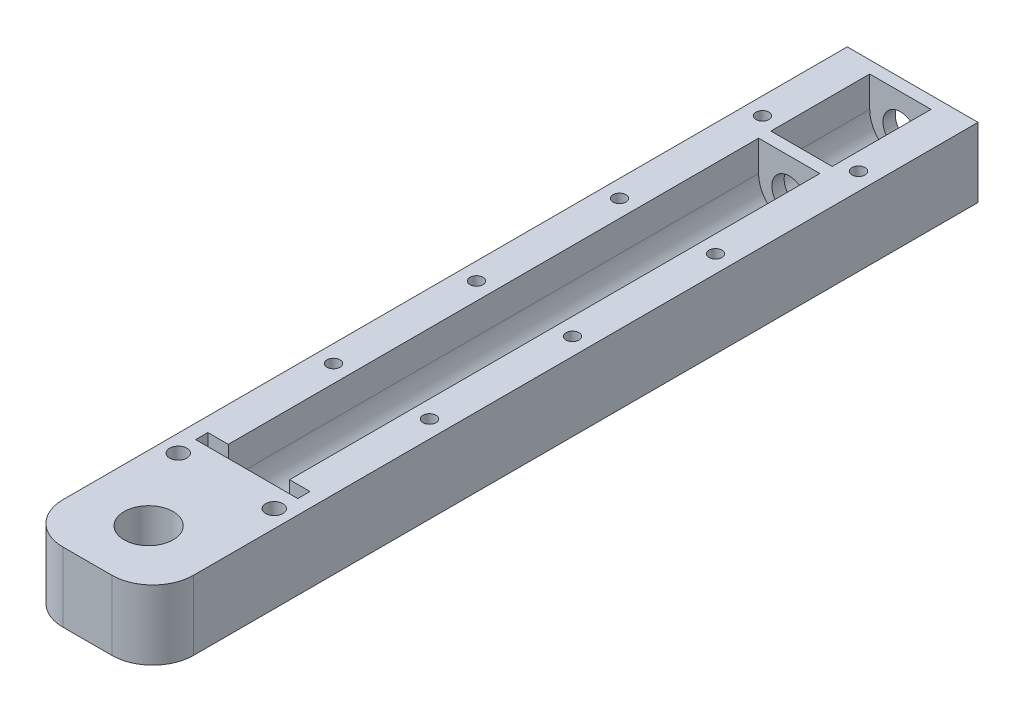
SolidWorks part; units mm, degrees
ref_plane "Front Plane" through (0, 0, 0) normal (0, 0, 1) x (1, 0, 0)
ref_plane "Top Plane" through (0, 0, 0) normal (0, 1, 0) x (1, 0, 0)
ref_plane "Right Plane" through (0, 0, 0) normal (1, 0, 0) x (0, 0, -1)
sketch "Sketch1" plane through (0, 0, 0) normal (0, 0, 1) x (1, 0, 0)
  line L1 (-16, 8.5) -> (16, 8.5)
  line L2 (-16, 8.5) -> (-16, -8.5)
  line L3 (-16, -8.5) -> (16, -8.5)
  line L4 (16, 8.5) -> (16, -8.5)
  line L5 (-16, 8.5) -> (16, -8.5) construction
  line L6 (-16, -8.5) -> (16, 8.5) construction
  circle A0 centre (0, 0) radius 4.25
  point P0 (0, 0)
  dimension "D3" = 8.5
  dimension "D1" = 17
  dimension "D2" = 32
extrude "Boss-Extrude1" add sketch "Sketch1" along normal blind 3
sketch "Sketch2" plane through (0, 0, 3) normal (0, 0, 1) x (1, 0, 0)
  line L0 (-7.5, 1) -> (-7.5, 8.5)
  line L1 (16, -8.5) -> (-16, -8.5)
  line L2 (16, -8.5) -> (16, 8.5)
  line L3 (16, 8.5) -> (7.5, 8.5)
  line L4 (-16, -8.5) -> (-16, 8.5)
  line L5 (16, -8.5) -> (-16, 8.5) construction
  line L6 (16, 8.5) -> (-16, -8.5) construction
  line L7 (7.5, 1) -> (7.5, 8.5)
  line L8 (-16, 8.5) -> (-7.5, 8.5)
  arc A0 (-7.5, 1) -> (7.5, 1) centre (0, 1) ccw
  point P0 (0, 0)
  point P9 (0, -6.5)
  dimension "D1" = 15
  dimension "D2" = 2
extrude "Boss-Extrude2" add sketch "Sketch2" along normal blind 24.2
sketch "Sketch3" plane through (0, 0, 27.2) normal (0, 0, 1) x (1, 0, 0)
  line L1 (-16, -8.5) -> (16, -8.5)
  line L2 (-16, -8.5) -> (-16, 8.5)
  line L3 (-16, 8.5) -> (16, 8.5)
  line L4 (16, -8.5) -> (16, 8.5)
  line L5 (-16, -8.5) -> (16, 8.5) construction
  line L6 (-16, 8.5) -> (16, -8.5) construction
  circle A0 centre (0, 0) radius 4.25
extrude "Boss-Extrude3" add sketch "Sketch3" along normal blind 3
sketch "Sketch4" plane through (0, 0, 30.2) normal (0, 0, 1) x (1, 0, 0)
  line L1 (16, -8.5) -> (-16, -8.5)
  line L2 (16, -8.5) -> (16, 8.5)
  line L3 (16, 8.5) -> (7.5, 8.5)
  line L4 (-16, -8.5) -> (-16, 8.5)
  line L5 (16, -8.5) -> (-16, 8.5) construction
  line L6 (16, 8.5) -> (-16, -8.5) construction
  line L7 (-7.5, 1) -> (-7.5, 8.5)
  line L8 (7.5, 1) -> (7.5, 8.5)
  line L9 (-7.5, 8.5) -> (-16, 8.5)
  arc A0 (-7.5, 1) -> (7.5, 1) centre (0, 1) ccw
  point P0 (0, 0)
  point P8 (0, -6.5)
  point P13 (0, 8.5)
  dimension "D1" = 15
  dimension "D2" = 2
extrude "Boss-Extrude4" add sketch "Sketch4" along normal blind 129.8
sketch "Sketch5" plane through (0, 0, 160) normal (0, 0, 1) x (1, 0, 0)
  line L1 (16, -8.5) -> (-16, -8.5)
  line L2 (16, -8.5) -> (16, 8.5)
  line L3 (16, 8.5) -> (-16, 8.5)
  line L4 (-16, -8.5) -> (-16, 8.5)
  line L5 (16, -8.5) -> (-16, 8.5) construction
  line L6 (16, 8.5) -> (-16, -8.5) construction
  point P0 (0, 0)
extrude "Boss-Extrude5" add sketch "Sketch5" along normal blind 18
sketch "Sketch6" plane through (0, 8.5, 0) normal (0, 1, 0) x (1, 0, 0)
  line L0 (7.5, -160) -> (-7.5, -160) construction
  line L1 (-12.5, -160) -> (12.5, -160)
  line L2 (-12.5, -160) -> (-12.5, -163)
  line L3 (-12.5, -163) -> (12.5, -163)
  line L4 (12.5, -160) -> (12.5, -163)
  line L6 (7.5, -160) -> (-7.5, -160) construction
  point P6 (0, -160)
  point P10 (0, -160)
  dimension "D1" = 3
  dimension "D2" = 25
extrude "Cut-Extrude1" cut sketch "Sketch6" against normal blind 15
sketch "Sketch7" plane through (0, 8.5, 0) normal (0, 1, 0) x (1, 0, 0)
  line L1 (-16, -178) -> (16, -178)
  line L2 (-16, -178) -> (-16, -192)
  line L3 (-6, -202) -> (6, -202)
  line L4 (16, -178) -> (16, -192)
  arc A0 (16, -192) -> (6, -202) centre (6, -192) cw
  arc A1 (-16, -192) -> (-6, -202) centre (-6, -192) ccw
  point P6 (16, -178)
  dimension "D1" = 10
  dimension "D2" = 24
extrude "Boss-Extrude6" add sketch "Sketch7" against normal up to vertex (17 mm away) up to point (-16, -8.5, 178)
sketch "Sketch8" plane through (0, 8.5, 0) normal (0, 1, 0) x (1, 0, 0)
  line L0 (0, -202) -> (0, -187) construction
  line L1 (-6, -202) -> (6, -202) construction
  circle A0 centre (0, -187) radius 6
  dimension "D1" = 12
  dimension "D2" = 15
extrude "Cut-Extrude2" cut sketch "Sketch8" against normal blind 46
sketch "Sketch9" plane through (0, 8.5, 0) normal (0, 1, 0) x (1, 0, 0)
  line L0 (0, -202) -> (0, -30.2) construction
  line L1 (-7.5, -30.2) -> (7.5, -30.2) construction
  line L2 (11.75, -130) -> (11.75, -95) construction
  line L3 (-12.5, -163) -> (12.5, -163) construction
  line L4 (7.5, -160) -> (16, -160)
  line L5 (11.75, -160) -> (11.75, -130) construction
  line L6 (-16, 0) -> (-16, -192)
  line L7 (-6, -202) -> (6, -202)
  line L8 (16, -192) -> (16, 0)
  line L9 (16, 0) -> (-16, 0)
  line L10 (-16, 0) -> (-16, -192)
  line L11 (-6, -202) -> (6, -202)
  line L12 (16, -192) -> (16, 0)
  line L13 (16, 0) -> (-16, 0)
  circle A0 centre (11.75, -130) radius 1.5875
  circle A1 centre (-11.75, -130) radius 1.5875
  arc A2 (-16, -192) -> (-6, -202) centre (-6, -192) ccw
  arc A3 (6, -202) -> (16, -192) centre (6, -192) ccw
  arc A4 (-16, -192) -> (-6, -202) centre (-6, -192) ccw
  arc A5 (6, -202) -> (16, -192) centre (6, -192) ccw
  circle A6 centre (11.75, -95) radius 1.5875
  circle A7 centre (-11.75, -95) radius 1.5875
  circle A8 centre (11.75, -60) radius 1.5875
  circle A9 centre (11.75, -25) radius 1.5875
  circle A14 centre (-11.75, -25) radius 1.5875
  circle A15 centre (-11.75, -60) radius 1.5875
  circle A16 centre (11.75, 10) radius 1.5875 [skipped]
  circle A17 centre (11.75, 45) radius 1.5875 [skipped]
  circle A18 centre (11.75, -168) radius 2.1143
  circle A19 centre (-11.75, -168) radius 2.1143
  circle A20 centre (0, -187) radius 6 construction
  circle A21 centre (0, -187) radius 6
  point P35 (0, -181)
  dimension "D3" = 3.175
  dimension "D5" = 3.175
  dimension "D7" = 35
  dimension "D8" = 4.2287
  dimension "D9" = 38
  dimension "D1" = 0
  dimension "D2" = 30
  dimension "D4" = 35
  dimension "D10" = 25
  dimension "D11" = 18
  dimension "D6" = 5
extrude "Cut-Extrude3" cut sketch "Sketch9" against normal blind 46 contours A0 | A6 | A1 | A7 | A15 | A8 | A9 | A14 | A18 | A19 region at (11.75, 8.5, 130) region at (-11.75, 8.5, 130) region at (11.75, 8.5, 95) region at (-11.75, 8.5, 95) region at (11.75, 8.5, 60) region at (11.75, 8.5, 25) region at (-11.75, 8.5, 25) region at (-11.75, 8.5, 60) region at (11.75, 8.5, 168)
sketch "Sketch10" plane through (0, -8.5, 0) normal (0, -1, 0) x (1, 0, 0)
  line L0 (-15.214, 25) -> (-13.482, 22)
  line L1 (-13.482, 28) -> (-10.018, 28)
  line L3 (-13.482, 22) -> (-10.018, 22)
  line L5 (-13.482, 22) -> (-10.018, 28) construction
  line L6 (-13.482, 28) -> (-10.018, 22) construction
  line L7 (-8.286, 25) -> (-10.018, 22)
  line L8 (-15.214, 25) -> (-13.482, 28)
  line L9 (-8.286, 25) -> (-10.018, 28)
  line L10 (0, 0) -> (0, 202) construction
  line L11 (-16, 0) -> (16, 0) construction
  line L12 (-6, 202) -> (6, 202) construction
  line L13 (13.482, 28) -> (10.018, 28)
  line L14 (8.286, 25) -> (10.018, 28)
  line L15 (8.286, 25) -> (10.018, 22)
  line L16 (13.482, 22) -> (10.018, 22)
  line L17 (15.214, 25) -> (13.482, 22)
  line L18 (15.214, 25) -> (13.482, 28)
  line L61 (13.482, 171.2837) -> (10.018, 171.2837)
  line L62 (8.286, 168.2837) -> (10.018, 171.2837)
  line L63 (8.286, 168.2837) -> (10.018, 165.2837)
  line L64 (13.482, 165.2837) -> (10.018, 165.2837)
  line L65 (15.214, 168.2837) -> (13.482, 165.2837)
  line L66 (15.214, 168.2837) -> (13.482, 171.2837)
  line L70 (-11.75, 95) -> (-11.75, 135.0869) construction
  line L71 (-10.0179, 57) -> (-8.2859, 60)
  line L81 (-8.2859, 60) -> (-10.0179, 63)
  line L82 (-10.0179, 63) -> (-13.4821, 63)
  line L83 (-13.4821, 63) -> (-15.2141, 60)
  line L84 (-15.2141, 60) -> (-13.4821, 57)
  line L85 (-13.4821, 57) -> (-10.0179, 57)
  line L86 (13.4821, 57) -> (15.2141, 60)
  line L87 (15.2141, 60) -> (13.4821, 63)
  line L88 (13.482, 135.4628) -> (10.018, 135.4628) [skipped]
  line L89 (8.286, 132.4628) -> (10.018, 135.4628) [skipped]
  line L90 (8.286, 132.4628) -> (10.018, 129.4628) [skipped]
  line L91 (13.482, 129.4628) -> (10.018, 129.4628) [skipped]
  line L92 (15.214, 132.4628) -> (13.482, 129.4628) [skipped]
  line L93 (15.214, 132.4628) -> (13.482, 135.4628) [skipped]
  line L94 (13.4821, 63) -> (10.0179, 63)
  line L95 (10.0179, 63) -> (8.2859, 60)
  line L96 (8.2859, 60) -> (10.0179, 57)
  line L97 (10.0179, 57) -> (13.4821, 57)
  line L98 (13.4821, 92) -> (15.2141, 95)
  line L99 (15.2141, 95) -> (13.4821, 98)
  line L100 (13.482, 99.6419) -> (10.018, 99.6419) [skipped]
  line L101 (8.286, 96.6419) -> (10.018, 99.6419) [skipped]
  line L102 (8.286, 96.6419) -> (10.018, 93.6419) [skipped]
  line L103 (13.482, 93.6419) -> (10.018, 93.6419) [skipped]
  line L104 (15.214, 96.6419) -> (13.482, 93.6419) [skipped]
  line L105 (15.214, 96.6419) -> (13.482, 99.6419) [skipped]
  line L106 (13.4821, 98) -> (10.0179, 98)
  line L107 (10.0179, 98) -> (8.2859, 95)
  line L108 (8.2859, 95) -> (10.0179, 92)
  line L109 (10.0179, 92) -> (13.4821, 92)
  line L110 (-10.0179, 92) -> (-8.2859, 95)
  line L111 (-8.2859, 95) -> (-10.0179, 98)
  line L112 (13.482, 63.8209) -> (10.018, 63.8209) [skipped]
  line L113 (8.286, 60.8209) -> (10.018, 63.8209) [skipped]
  line L114 (8.286, 60.8209) -> (10.018, 57.8209) [skipped]
  line L115 (13.482, 57.8209) -> (10.018, 57.8209) [skipped]
  line L116 (15.214, 60.8209) -> (13.482, 57.8209) [skipped]
  line L117 (15.214, 60.8209) -> (13.482, 63.8209) [skipped]
  line L118 (-10.0179, 98) -> (-13.4821, 98)
  line L119 (-13.4821, 98) -> (-15.2141, 95)
  line L120 (-15.2141, 95) -> (-13.4821, 92)
  line L121 (-13.4821, 92) -> (-10.0179, 92)
  line L122 (-10.0179, 127.2) -> (-8.2859, 130.2)
  line L123 (-8.2859, 130.2) -> (-10.0179, 133.2)
  line L124 (-10.0179, 133.2) -> (-13.4821, 133.2)
  line L125 (-13.4821, 133.2) -> (-15.2141, 130.2)
  line L126 (-15.2141, 130.2) -> (-13.4821, 127.2)
  line L127 (-13.4821, 127.2) -> (-10.0179, 127.2)
  line L129 (-10.0179, 165) -> (-8.2859, 168)
  line L130 (-8.2859, 168) -> (-10.0179, 171)
  line L131 (-10.0179, 171) -> (-13.4821, 171)
  line L132 (-13.4821, 171) -> (-15.2141, 168)
  line L133 (-15.2141, 168) -> (-13.4821, 165)
  line L134 (-13.4821, 165) -> (-10.0179, 165)
  line L135 (10.0491, 127.2504) -> (13.2808, 127.1522)
  line L136 (13.2808, 127.1522) -> (14.9817, 129.9018)
  line L137 (14.9817, 129.9018) -> (13.4509, 132.7496)
  line L138 (13.4509, 132.7496) -> (10.2192, 132.8478)
  line L139 (10.2192, 132.8478) -> (8.5183, 130.0982)
  line L140 (8.5183, 130.0982) -> (10.0491, 127.2504)
  circle A0 centre (-11.75, 95) radius 1.5875 construction
  circle A3 centre (-11.75, 168) radius 3 construction
  circle A5 centre (11.75, 168) radius 2.1143 construction
  circle A6 centre (-11.75, 168) radius 2.1143 construction
  circle A7 centre (11.75, 130) radius 2.8 construction
  circle A11 centre (11.75, 25) radius 1.5875 construction
  circle A12 centre (-11.75, 25) radius 1.5875 construction
  circle A13 centre (11.75, 168) radius 2.1143
  circle A14 centre (-11.75, 168) radius 2.1143
  circle A19 centre (11.75, 25) radius 1.5875
  circle A20 centre (-11.75, 25) radius 1.5875
  circle A21 centre (11.75, 95) radius 1.5875 construction
  circle A22 centre (11.75, 60) radius 1.5875 construction
  circle A23 centre (-11.75, 60) radius 1.5875 construction
  circle A24 centre (-11.75, 95) radius 1.5875
  circle A25 centre (11.75, 95) radius 1.5875
  circle A26 centre (11.75, 60) radius 1.5875
  circle A27 centre (-11.75, 60) radius 1.5875
  circle A28 centre (-11.75, 60) radius 3 construction
  circle A29 centre (11.75, 60) radius 3 construction
  circle A30 centre (11.75, 95) radius 3 construction
  circle A31 centre (-11.75, 95) radius 3 construction
  point P0 (-11.75, 25)
  point P31 (-11.75, 171)
  dimension "D9" = 6
  dimension "D1" = 6
  dimension "D2" = 6.928
  dimension "D3" = 3.464
  dimension "D6" = 2
  dimension "D7" = 6
  dimension "D8" = 6
  dimension "D4" = 6
  dimension "D10" = 6
  dimension "D11" = 6.9282
  dimension "D12" = 6
  dimension "D5" = 5
sketch "Sketch12" plane through (0, 8.5, 0) normal (0, 1, 0) x (1, 0, 0)
  line L0 (-12.5, -163) -> (12.5, -163) construction
  line L1 (-12.5, -163) -> (12.5, -163)
  line L4 (-16, 0) -> (-16, -192)
  line L5 (-6, -202) -> (6, -202)
  line L6 (16, -192) -> (16, 0)
  line L7 (16, 0) -> (-16, 0)
  line L8 (-16, 0) -> (-16, -192)
  line L9 (-6, -202) -> (6, -202)
  line L10 (16, -192) -> (16, 0)
  line L11 (16, 0) -> (-16, 0)
  circle A0 centre (-11.75, -3.5) radius 1.5875 construction
  arc A2 (-16, -192) -> (-6, -202) centre (-6, -192) ccw
  arc A3 (6, -202) -> (16, -192) centre (6, -192) ccw
  arc A4 (-16, -192) -> (-6, -202) centre (-6, -192) ccw
  arc A5 (6, -202) -> (16, -192) centre (6, -192) ccw
  point P8 (0, -163)
  dimension "D3" = 3.5
  dimension "D4" = 4.25
  dimension "D2" = 163
  dimension "D1" = 0
extrude "Cut-Extrude4" cut sketch "Sketch10" against normal blind 4
sketch "Sketch13" plane through (0, 8.5, 0) normal (0, 1, 0) x (1, 0, 0)
  line L0 (0, -160) -> (-12.5, -160) construction
  line L1 (-16, 0) -> (-16, -192) construction
  line L2 (0, -160) -> (-12.5, -160)
  line L3 (-16, 0) -> (-16, -192)
  line L4 (-16, 0) -> (-16, -192)
  line L5 (-6, -202) -> (6, -202)
  line L6 (16, -192) -> (16, 0)
  line L7 (16, 0) -> (-16, 0)
  line L8 (-16, 0) -> (-16, -192)
  line L9 (-6, -202) -> (6, -202)
  line L10 (16, -192) -> (16, 0)
  line L11 (16, 0) -> (-16, 0)
  line L13 (-7.5, -30.2) -> (7.5, -30.2) construction
  line L14 (-7.5, -30.2) -> (7.5, -30.2)
  arc A2 (-16, -192) -> (-6, -202) centre (-6, -192) ccw
  arc A3 (6, -202) -> (16, -192) centre (6, -192) ccw
  arc A4 (-16, -192) -> (-6, -202) centre (-6, -192) ccw
  arc A5 (6, -202) -> (16, -192) centre (6, -192) ccw
  dimension "D2" = 160
  dimension "D3" = 30.2
  dimension "D1" = 0
